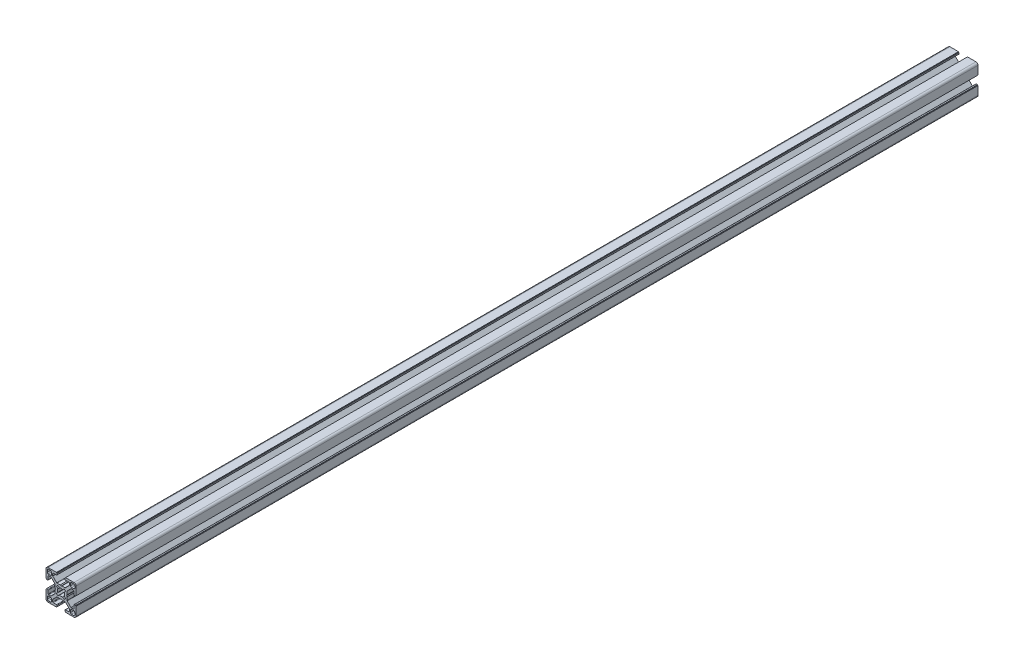
SolidWorks part; units mm, degrees
ref_plane "Front Plane" through (0, 0, 0) normal (0, 0, 1) x (1, 0, 0)
ref_plane "Top Plane" through (0, 0, 0) normal (0, 1, 0) x (1, 0, 0)
ref_plane "Right Plane" through (0, 0, 0) normal (1, 0, 0) x (0, 0, -1)
sketch "Sketch1" plane through (0, 0, 0) normal (0, 0, 1) x (1, 0, 0)
  line L0 (-15, 0) -> (15, 0) construction
  line L1 (0, -15) -> (0, 15) construction
  line L2 (-4.5, 15) -> (4.5, 15) construction
  line L3 (-4, -15) -> (4, -15) construction
  line L4 (-4.5, 15) -> (-4.5, 14.5)
  line L5 (-4.5, 14.5) -> (-4, 14.5)
  line L6 (-4, 14.5) -> (-4, 13.29)
  line L7 (-4.5, 12.79) -> (-7.7675, 12.79)
  line L8 (-8.2675, 12.29) -> (-8.2675, 10.2707)
  line L9 (-8.1211, 9.9171) -> (-4.3504, 6.1464)
  line L10 (-3.9968, 6) -> (0, 6)
  line L11 (0, 0) -> (-15, 15) construction
  line L12 (-4.5, 15) -> (-12.968, 15)
  line L14 (-12.705, 9.5135) -> (-10.5135, 9.5135)
  line L15 (-13.705, 10.5135) -> (-13.705, 12.705)
  line L16 (-12.705, 13.705) -> (-10.5135, 13.705)
  line L17 (-9.5135, 10.5135) -> (-9.5135, 12.705)
  line L18 (-13.705, 9.5135) -> (-9.5135, 13.705) construction
  line L19 (-13.705, 13.705) -> (-9.5135, 9.5135) construction
  line L20 (-3.1568, 4.5038) -> (-1.5303, 3.1477) construction
  line L21 (-4.5038, 3.1568) -> (-3.1477, 1.5303) construction
  line L22 (-6, 3.9968) -> (-6, 0)
  line L23 (-9.9171, 8.1211) -> (-6.1464, 4.3504)
  line L24 (-15, 4.5) -> (-15, 12.968)
  line L25 (-12.29, 8.2675) -> (-10.2707, 8.2675)
  line L26 (-12.79, 4.5) -> (-12.79, 7.7675)
  line L27 (-14.5, 4) -> (-13.29, 4)
  line L28 (-14.5, 4.5) -> (-14.5, 4)
  line L29 (-15, 4.5) -> (-14.5, 4.5)
  circle A0 centre (0, 0) radius 3.5
  arc A1 (-12.968, 15) -> (-15, 12.968) centre (-12.968, 12.968) ccw
  circle A2 centre (0, 0) radius 5.5 construction
  arc A3 (-10.5135, 9.5135) -> (-9.5135, 10.5135) centre (-10.5135, 10.5135) ccw
  arc A4 (-13.705, 12.705) -> (-12.705, 13.705) centre (-12.705, 12.705) cw
  arc A5 (-10.5135, 13.705) -> (-9.5135, 12.705) centre (-10.5135, 12.705) cw
  arc A6 (-12.705, 9.5135) -> (-13.705, 10.5135) centre (-12.705, 10.5135) cw
  arc A7 (-12.79, 4.5) -> (-13.29, 4) centre (-13.29, 4.5) cw
  arc A8 (-12.29, 8.2675) -> (-12.79, 7.7675) centre (-12.29, 7.7675) ccw
  arc A9 (-9.9171, 8.1211) -> (-10.2707, 8.2675) centre (-10.2707, 7.7675) ccw
  arc A10 (-6, 3.9968) -> (-6.1464, 4.3504) centre (-6.5, 3.9968) ccw
  arc A11 (-4.3504, 6.1464) -> (-3.9968, 6) centre (-3.9968, 6.5) ccw
  arc A12 (-4, 13.29) -> (-4.5, 12.79) centre (-4.5, 13.29) cw
  arc A13 (-7.7675, 12.79) -> (-8.2675, 12.29) centre (-7.7675, 12.29) ccw
  arc A14 (-8.2675, 10.2707) -> (-8.1211, 9.9171) centre (-7.7675, 10.2707) ccw
  point P4 (0, 0)
  point P8 (0, 0)
  point P13 (0, 15)
  point P15 (0, -15)
  point P16 (0, 6)
  point P23 (-11.6092, 11.6093)
  point P26 (0, 6)
  point P62 (-12.79, 4)
  point P65 (-12.79, 8.2675)
  point P68 (-10.0636, 8.2675)
  point P71 (-6, 4.2039)
  point P74 (-4.2039, 6)
  point P77 (-4, 12.79)
  point P80 (-8.2675, 12.79)
  point P83 (-8.2675, 10.0636)
  dimension "Center Hole Diameter" = 7
  dimension "D11" = 2.032
  dimension "D9" = 11
  dimension "D13" = 1
  dimension "D14" = 0.5
  dimension "Rail Height" = 30
  dimension "Rail Width" = 30
  dimension "T-Slot Width" = 8
  dimension "T-Slot Depth" = 9
  dimension "D1" = 9
  dimension "D2" = 45
  dimension "D3" = 8
  dimension "D4" = 2.21
  dimension "D5" = 16.535
  dimension "D7" = 2.54
  dimension "D6" = 1.295
  dimension "D8" = 1.246
  dimension "D10" = 10.36
  dimension "D12" = 1.905
sketch "Sketch2" plane through (0, 0, 0) normal (1, 0, 0) x (0, 0, -1)
  line L0 (-76.2, 0) -> (76.2, 0) construction
  line L2 (0, -15) -> (0, 15) construction
  line L3 (0, -15) -> (0, 15) construction
  line L4 (-76.2, -15) -> (-76.2, 15) construction
  line L5 (76.2, -15) -> (76.2, 15) construction
  point P0 (-38.7, 0)
  point P3 (0, 0)
  point P4 (38.7, 0)
  point P12 (-76.2, 0)
  point P14 (76.2, 0)
  dimension "Length" = 152.4
  dimension "D1" = 37.5
sketch "Sketch3" plane through (0, 0, 0) normal (0, 0, 1) x (1, 0, 0)
  line L0 (-4.5038, 3.1568) -> (-3.1477, 1.5303)
  line L1 (0, 3.5) -> (0, 5.5)
  line L2 (-5.5, 0) -> (-3.5, 0)
  line L7 (-6, 3.9968) -> (-6, 0) construction
  line L31 (-9.9171, 8.1211) -> (-6.1464, 4.3504) construction
  line L117 (-12.29, 8.2675) -> (-10.2707, 8.2675) construction
  line L118 (-12.79, 4.5) -> (-12.79, 7.7675) construction
  line L157 (-12.705, 9.5135) -> (-10.5135, 9.5135)
  line L158 (-9.5135, 10.5135) -> (-9.5135, 12.705)
  line L163 (-10.5135, 13.705) -> (-12.705, 13.705)
  line L164 (-13.705, 12.705) -> (-13.705, 10.5135)
  line L165 (-12.705, 9.5135) -> (-10.5135, 9.5135)
  line L166 (-9.5135, 10.5135) -> (-9.5135, 12.705)
  line L167 (-10.5135, 13.705) -> (-12.705, 13.705)
  line L168 (-13.705, 12.705) -> (-13.705, 10.5135)
  line L169 (-14.5, 4) -> (-13.29, 4) construction
  line L170 (-14.5, 4.5) -> (-14.5, 4) construction
  line L171 (-15, 4.5) -> (-14.5, 4.5) construction
  line L172 (-15, 4.5) -> (-15, 12.968) construction
  line L173 (-4.5, 15) -> (-12.968, 15) construction
  line L174 (-4.5, 15) -> (-4.5, 14.5) construction
  line L175 (-4.5, 14.5) -> (-4, 14.5) construction
  line L176 (-4, 14.5) -> (-4, 13.29) construction
  line L177 (-4.5, 12.79) -> (-7.7675, 12.79) construction
  line L178 (-8.2675, 12.29) -> (-8.2675, 10.2707) construction
  line L179 (-8.1211, 9.9171) -> (-4.3504, 6.1464) construction
  line L180 (-3.9968, 6) -> (0, 6) construction
  line L181 (-6, 3.9968) -> (-6, 0.866)
  line L182 (-9.9171, 8.1211) -> (-6.1464, 4.3504)
  line L183 (-12.29, 8.2675) -> (-10.2707, 8.2675)
  line L184 (-12.79, 4.5) -> (-12.79, 7.7675)
  line L185 (-14.5, 4) -> (-13.29, 4)
  line L186 (-14.5, 4.5) -> (-14.5, 4)
  line L187 (-15, 4.5) -> (-14.5, 4.5)
  line L188 (-15, 4.5) -> (-15, 12.968)
  line L189 (-4.5, 15) -> (-12.968, 15)
  line L190 (-4.5, 15) -> (-4.5, 14.5)
  line L191 (-4.5, 14.5) -> (-4, 14.5)
  line L192 (-4, 14.5) -> (-4, 13.29)
  line L193 (-4.5, 12.79) -> (-7.7675, 12.79)
  line L194 (-8.2675, 12.29) -> (-8.2675, 10.2707)
  line L195 (-8.1211, 9.9171) -> (-4.3504, 6.1464)
  line L196 (-3.9968, 6) -> (-0.866, 6)
  line L197 (-0.866, 6) -> (0, 5.5)
  line L198 (0, -15) -> (0, 15) construction
  line L199 (0, 0) -> (-15, 15) construction
  line L200 (0, 0) -> (-15, 15) construction
  line L201 (-3.1568, 4.5038) -> (-1.5303, 3.1477) construction
  line L202 (-3.1568, 4.5038) -> (-1.5303, 3.1477)
  line L203 (-6, 0.866) -> (-5.5, 0)
  line L204 (-15, 0) -> (15, 0) construction
  line L205 (-15, 0) -> (15, 0) construction
  line L206 (0, -15) -> (0, 15) construction
  arc A0 (-3.5, 0) -> (-3.1477, 1.5303) centre (0, 0) cw
  arc A10 (-6, 3.9968) -> (-6.1464, 4.3504) centre (-6.5, 3.9968) ccw construction
  circle A16 centre (0, 0) radius 3.5
  arc A18 (0, 3.5) -> (-1.5303, 3.1477) centre (0, 0) ccw
  arc A20 (-9.9171, 8.1211) -> (-10.2707, 8.2675) centre (-10.2707, 7.7675) ccw construction
  arc A22 (-12.29, 8.2675) -> (-12.79, 7.7675) centre (-12.29, 7.7675) ccw construction
  arc A28 (-13.29, 4) -> (-12.79, 4.5) centre (-13.29, 4.5) ccw construction
  arc A29 (-10.5135, 9.5135) -> (-9.5135, 10.5135) centre (-10.5135, 10.5135) ccw
  arc A30 (-9.5135, 12.705) -> (-10.5135, 13.705) centre (-10.5135, 12.705) ccw
  arc A31 (-12.705, 13.705) -> (-13.705, 12.705) centre (-12.705, 12.705) ccw
  arc A32 (-13.705, 10.5135) -> (-12.705, 9.5135) centre (-12.705, 10.5135) ccw
  arc A33 (-10.5135, 9.5135) -> (-9.5135, 10.5135) centre (-10.5135, 10.5135) ccw
  arc A34 (-9.5135, 12.705) -> (-10.5135, 13.705) centre (-10.5135, 12.705) ccw
  arc A35 (-12.705, 13.705) -> (-13.705, 12.705) centre (-12.705, 12.705) ccw
  arc A36 (-13.705, 10.5135) -> (-12.705, 9.5135) centre (-12.705, 10.5135) ccw
  arc A37 (-12.968, 15) -> (-15, 12.968) centre (-12.968, 12.968) ccw construction
  arc A38 (-4.5, 12.79) -> (-4, 13.29) centre (-4.5, 13.29) ccw construction
  arc A39 (-7.7675, 12.79) -> (-8.2675, 12.29) centre (-7.7675, 12.29) ccw construction
  arc A40 (-8.2675, 10.2707) -> (-8.1211, 9.9171) centre (-7.7675, 10.2707) ccw construction
  arc A41 (-4.3504, 6.1464) -> (-3.9968, 6) centre (-3.9968, 6.5) ccw construction
  arc A42 (-6, 3.9968) -> (-6.1464, 4.3504) centre (-6.5, 3.9968) ccw
  arc A43 (-9.9171, 8.1211) -> (-10.2707, 8.2675) centre (-10.2707, 7.7675) ccw
  arc A44 (-12.29, 8.2675) -> (-12.79, 7.7675) centre (-12.29, 7.7675) ccw
  arc A45 (-13.29, 4) -> (-12.79, 4.5) centre (-13.29, 4.5) ccw
  arc A46 (-12.968, 15) -> (-15, 12.968) centre (-12.968, 12.968) ccw
  arc A47 (-4.5, 12.79) -> (-4, 13.29) centre (-4.5, 13.29) ccw
  arc A48 (-7.7675, 12.79) -> (-8.2675, 12.29) centre (-7.7675, 12.29) ccw
  arc A49 (-8.2675, 10.2707) -> (-8.1211, 9.9171) centre (-7.7675, 10.2707) ccw
  arc A50 (-4.3504, 6.1464) -> (-3.9968, 6) centre (-3.9968, 6.5) ccw
  circle A51 centre (0, 0) radius 5.5 construction
  arc A52 (-3.1568, 4.5038) -> (-4.5038, 3.1568) centre (0, 0) ccw
  dimension "D3" = 60
  dimension "D4" = 60
  dimension "D1" = 0
  dimension "D2" = 0
extrude "Boss-Extrude1" add sketch "Sketch3" along normal mid plane 900
pattern_circular "CirPattern1" count 4 over 360 about axis through (0, 0, 76.2) along (0, 0, -1) of "Boss-Extrude1"
ref_plane "Contact Plane1" through (15, 0, 0) normal (1, 0, 0) x (0, 0, -1)
ref_plane "Contact Plane2" through (0, -15, 0) normal (0, 1, 0) x (1, 0, 0)
ref_plane "Contact Plane3" through (-15, 0, 0) normal (1, 0, 0) x (0, 0, -1)
ref_plane "Contact Plane4" through (0, 15, 0) normal (0, 1, 0) x (1, 0, 0)
equation "\"D1@Sketch2\" = \"Rail Height@Sketch1\" * 1.25"
equation "\"D1@Sketch1\"=\"T-Slot Width@Sketch1\"+1mm"
equation "\"D3@Sketch1\"=\"T-Slot Width@Sketch1\""
equation "\"D1@Boss-Extrude1\"=\"Length\""
equation "\"Length\" = 900mm"
